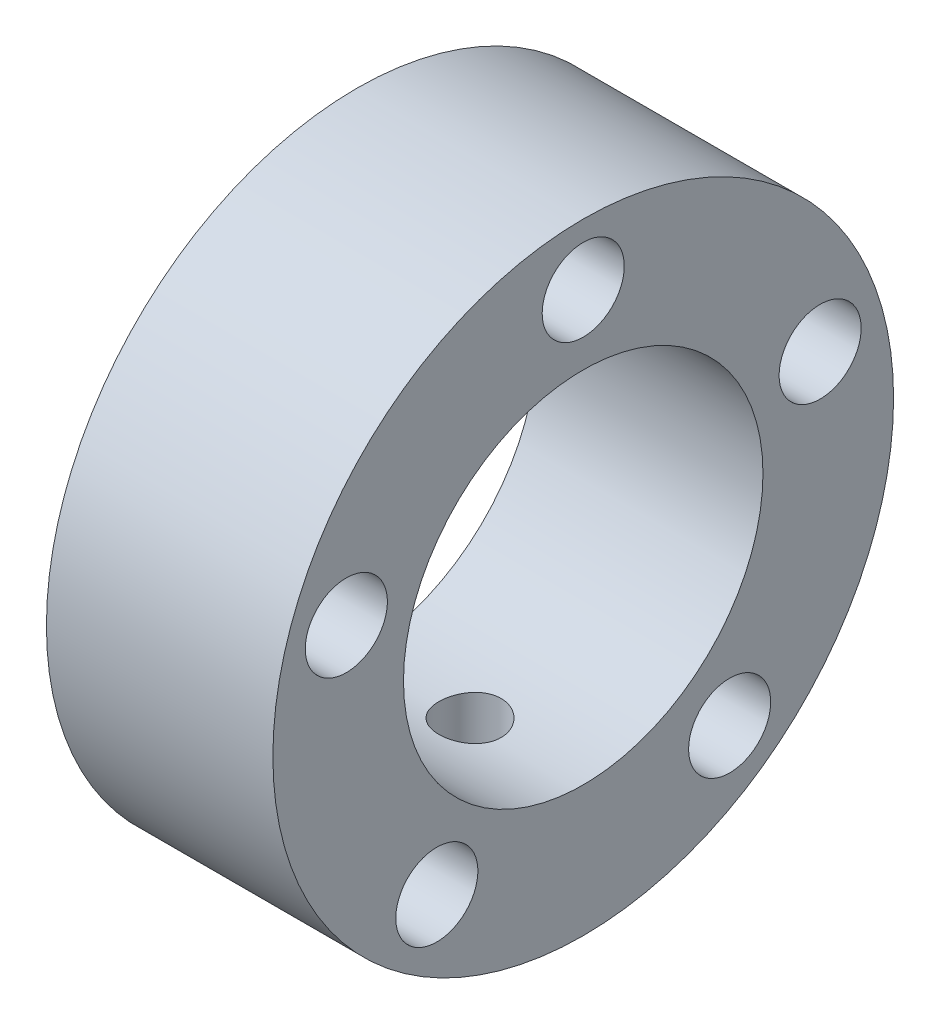
SolidWorks part; units mm, degrees
material "6061 Alloy"
ref_plane "Front Plane" through (0, 0, 0) normal (0, 0, 1) x (1, 0, 0)
ref_plane "Top Plane" through (0, 0, 0) normal (0, 1, 0) x (1, 0, 0)
ref_plane "Right Plane" through (0, 0, 0) normal (1, 0, 0) x (0, 0, -1)
sketch "Sketch1" plane through (0, 0, 0) normal (1, 0, 0) x (0, 0, -1)
  circle A0 centre (0, 0) radius 13.9245
  circle A1 centre (0, 0) radius 8.0645
  dimension "D1" = 16.129
extrude "Boss-Extrude1" add sketch "Sketch1" along normal blind 10.16
sketch "Sketch2" plane through (0, 0, 0) normal (-1, 0, 0) x (0, 0, 1)
  line L0 (0, 0) -> (0, 11.176) construction
  circle A0 centre (0, 11.176) radius 1.8415
  circle A1 centre (10.629, 3.4536) radius 1.8415
  circle A2 centre (6.5691, -9.0416) radius 1.8415
  circle A3 centre (-6.5691, -9.0416) radius 1.8415
  circle A4 centre (-10.629, 3.4536) radius 1.8415
  point P14 (0, 0)
  dimension "D1" = 5
  dimension "D2" = 3.683
  dimension "D3" = 11.176
extrude "Cut-Extrude1" cut sketch "Sketch2" against normal through all
sketch "Sketch3" plane through (0, 0, 0) normal (0, 1, 0) x (1, 0, 0)
  line L0 (0, 0) -> (10.16, 0) construction
  line L1 (0, 13.9245) -> (0, -13.9245) construction
  line L2 (10.16, -13.9245) -> (10.16, 13.9245) construction
  circle A0 centre (5.08, 0) radius 1.397
  dimension "D1" = 2.794
extrude "Cut-Extrude2" cut sketch "Sketch3" against normal through all
